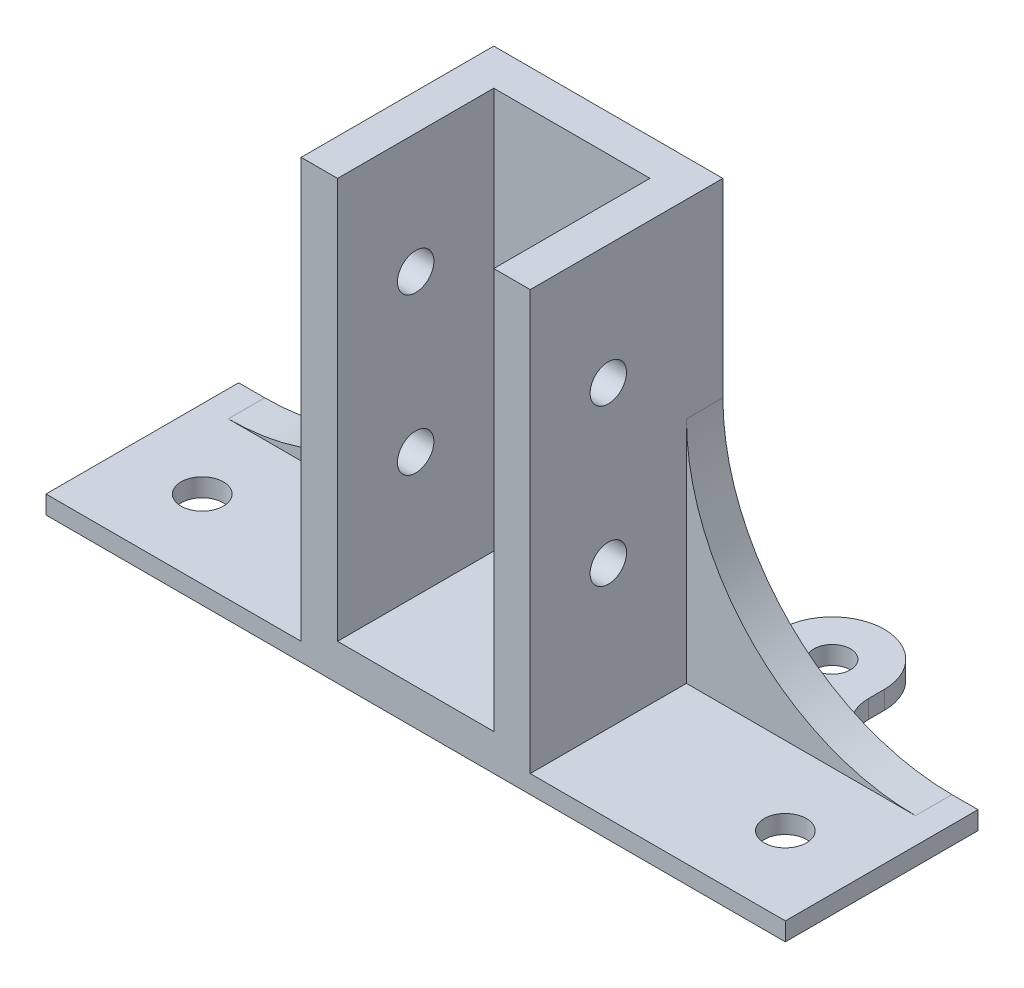
SolidWorks part; units mm, degrees
ref_plane "Front Plane" through (0, 0, 0) normal (0, 0, 1) x (1, 0, 0)
ref_plane "Top Plane" through (0, 0, 0) normal (0, 1, 0) x (1, 0, 0)
ref_plane "Right Plane" through (0, 0, 0) normal (1, 0, 0) x (0, 0, -1)
sketch "Sketch1" plane through (0, 0, 0) normal (0, 0, 1) x (1, 0, 0)
  line L1 (-16.1393, 44.8689) -> (5.8607, 44.8689)
  line L2 (-16.1393, 44.8689) -> (-16.1393, 2.8689)
  line L3 (-16.1393, 2.8689) -> (5.8607, 2.8689)
  line L4 (5.8607, 44.8689) -> (5.8607, 2.8689)
  dimension "D1" = 22
  dimension "D2" = 42
extrude "Boss-Extrude1" add sketch "Sketch1" along normal blind 18.5
sketch "Sketch2" plane through (0, 0, 18.5) normal (0, 0, 1) x (1, 0, 0)
  line L0 (5.8607, 44.8689) -> (-16.1393, 44.8689) construction
  line L1 (-12.6393, 44.8689) -> (2.3607, 44.8689)
  line L2 (-12.6393, 44.8689) -> (-12.6393, 6.3689)
  line L3 (-12.6393, 6.3689) -> (2.3607, 6.3689)
  line L4 (2.3607, 44.8689) -> (2.3607, 6.3689)
  line L5 (5.8607, 2.8689) -> (5.8607, 44.8689) construction
  line L6 (-16.1393, 2.8689) -> (5.8607, 2.8689) construction
  dimension "D1" = 15
  dimension "D2" = 3.5
  dimension "D3" = 3.5
extrude "Cut-Extrude1" cut sketch "Sketch2" against normal blind 15
sketch "Sketch3" plane through (0, 0, 0) normal (0, 0, -1) x (-1, 0, 0)
  line L1 (16.1393, 2.8689) -> (40.6393, 2.8689)
  line L2 (16.1393, 2.8689) -> (16.1393, 4.6189)
  line L3 (16.1393, 4.6189) -> (40.6393, 4.6189)
  line L4 (40.6393, 2.8689) -> (40.6393, 4.6189)
  line L5 (-5.8607, 2.8689) -> (-30.3607, 2.8689)
  line L6 (-5.8607, 2.8689) -> (-5.8607, 4.6189)
  line L7 (-5.8607, 4.6189) -> (-30.3607, 4.6189)
  line L8 (-30.3607, 2.8689) -> (-30.3607, 4.6189)
  dimension "D1" = 24.5
  dimension "D2" = 24.5
  dimension "D3" = 1.75
  dimension "D4" = 1.75
extrude "Boss-Extrude2" add sketch "Sketch3" against normal up to surface (18.5 mm away) up to face at (-5.1393, 24.7439, 18.5)
sketch "Sketch4" plane through (0, 0, 0) normal (0, 0, -1) x (-1, 0, 0)
  line L0 (38.1393, 4.6189) -> (16.1393, 4.6189)
  line L1 (40.6393, 4.6189) -> (16.1393, 4.6189) construction
  line L2 (16.1393, 4.6189) -> (16.1393, 26.6189)
  line L3 (16.1393, 44.8689) -> (16.1393, 4.6189) construction
  line L4 (-27.8607, 4.6189) -> (-5.8607, 4.6189)
  line L5 (-5.8607, 4.6189) -> (-30.3607, 4.6189) construction
  line L6 (-5.8607, 4.6189) -> (-5.8607, 26.6189)
  line L7 (-5.8607, 4.6189) -> (-5.8607, 44.8689) construction
  arc A0 (16.1393, 26.6189) -> (38.1393, 4.6189) centre (38.1393, 26.6189) ccw
  arc A1 (-5.8607, 26.6189) -> (-27.8607, 4.6189) centre (-27.8607, 26.6189) cw
  dimension "D1" = 22
extrude "Boss-Extrude3" add sketch "Sketch4" against normal blind 3.5
sketch "Sketch5" plane through (0, 2.8689, 0) normal (0, -1, 0) x (1, 0, 0)
  line L0 (-40.6393, 0) -> (30.3607, 0) construction
  line L1 (5.8607, 0) -> (-16.1393, 0) construction
  line L2 (15.8607, -5.5) -> (15.8607, 0)
  line L3 (-26.1393, -5.5) -> (-26.1393, 0)
  line L4 (-16.1393, -5.5) -> (-16.1393, 0)
  line L5 (5.8607, -5.5) -> (5.8607, 0)
  line L6 (15.8607, 0) -> (5.8607, 0)
  line L7 (-16.1393, 0) -> (-26.1393, 0)
  circle A0 centre (10.8607, -5.5) radius 1.75
  circle A1 centre (-21.1393, -5.5) radius 1.75
  arc A2 (5.8607, -5.5) -> (15.8607, -5.5) centre (10.8607, -5.5) ccw
  arc A3 (-26.1393, -5.5) -> (-16.1393, -5.5) centre (-21.1393, -5.5) ccw
  point P6 (-5.1393, 0)
  point P7 (-5.1393, 0)
  dimension "D4" = 3.5
  dimension "D1" = 5.5
  dimension "D2" = 16
  dimension "D3" = 16
extrude "Boss-Extrude4" add sketch "Sketch5" against normal up to surface (1.75 mm away) up to face at (-33.8893, 4.6189, 8.5833)
sketch "Sketch6" plane through (0, 4.6189, 0) normal (0, 1, 0) x (1, 0, 0)
  line L0 (30.3607, -11) -> (-40.6393, -11) construction
  line L1 (30.3607, -18.5) -> (30.3607, 0) construction
  line L2 (-40.6393, -18.5) -> (-40.6393, 0) construction
  line L3 (5.8607, -18.5) -> (30.3607, -18.5) construction
  circle A0 centre (22.8607, -11) radius 2.0274
  circle A1 centre (-33.1393, -11) radius 2.0274
  dimension "D2" = 7.5
  dimension "D3" = 7.5
  dimension "D1" = 7.5
extrude "Cut-Extrude2" cut sketch "Sketch6" against normal blind 10
fillet "Fillet1" radius 4 4 edges at (-26.1393, 3.7439, 0) (-16.1393, 3.7439, 0)
sketch "Sketch7" plane through (-16.1393, 0, 0) normal (-1, 0, 0) x (0, 0, 1)
  line L0 (11, 44.8689) -> (11, 4.6189) construction
  line L1 (18.5, 44.8689) -> (0, 44.8689) construction
  line L2 (18.5, 4.6189) -> (0, 4.6189) construction
  line L3 (18.5, 44.8689) -> (18.5, 4.6189) construction
  line L4 (3.5, 6.3689) -> (18.5, 6.3689) construction
  circle A0 centre (11, 33.3689) radius 1.75
  circle A1 centre (11, 18.3689) radius 1.75
  dimension "D2" = 3.5
  dimension "D1" = 7.5
  dimension "D3" = 15
  dimension "D4" = 12
extrude "Cut-Extrude3" cut sketch "Sketch7" against normal blind 28
sketch "Sketch8" plane through (0, 0, 0) normal (0, 0, -1) x (-1, 0, 0)
  line L0 (5.1393, 44.8689) -> (5.1393, 2.8689) construction
  line L1 (-5.8607, 44.8689) -> (16.1393, 44.8689) construction
  line L2 (12.1393, 2.8689) -> (-1.8607, 2.8689) construction
  line L3 (12.6393, 6.3689) -> (-2.3607, 6.3689) construction
  circle A0 centre (5.1393, 33.3689) radius 1.75
  circle A1 centre (5.1393, 18.3689) radius 1.75
  dimension "D1" = 15
  dimension "D2" = 12
  dimension "D3" = 3.5
extrude "Cut-Extrude4" cut sketch "Sketch8" against normal blind 28
